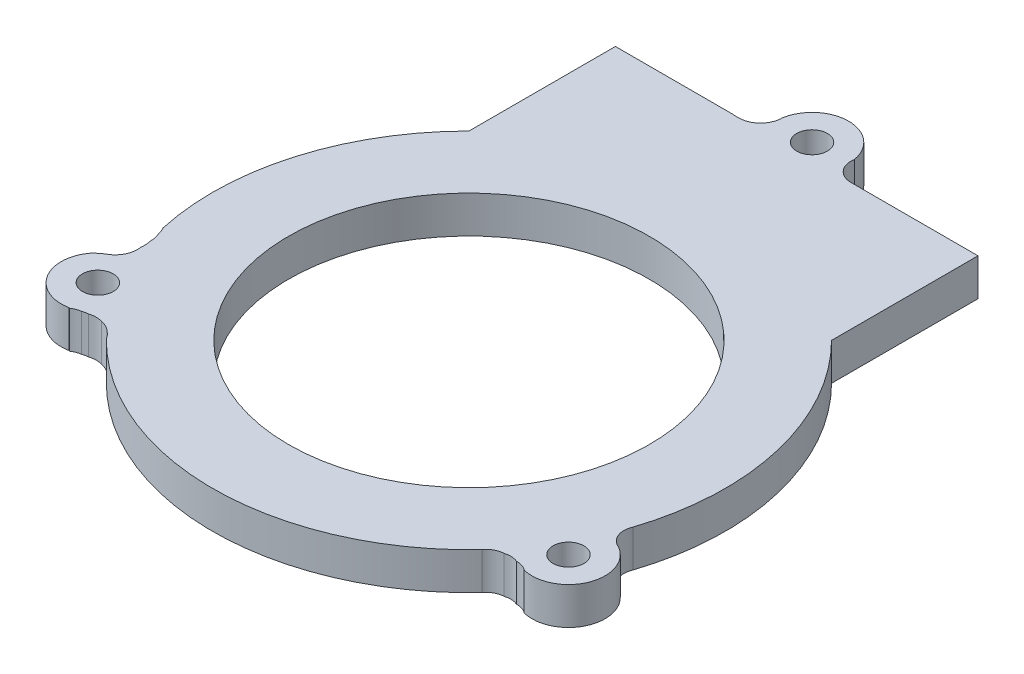
SolidWorks part; units mm, degrees
ref_plane "Front Plane" through (0, 0, 0) normal (0, 0, 1) x (1, 0, 0)
ref_plane "Top Plane" through (0, 0, 0) normal (0, 1, 0) x (1, 0, 0)
ref_plane "Right Plane" through (0, 0, 0) normal (1, 0, 0) x (0, 0, -1)
sketch "Sketch13" plane through (0, 0, 0) normal (0, 1, 0) x (1, 0, 0)
  circle A0 centre (0, 0) radius 35
extrude "Boss-Extrude3" add sketch "Sketch13" along normal blind 5.08
sketch "Sketch14" plane through (0, 5.08, 0) normal (0, 1, 0) x (1, 0, 0)
  line L0 (-24.7478, 24.7497) -> (24.7477, 24.7498)
  line L1 (-24.7478, 24.7497) -> (-24.7479, 44.7452)
  line L2 (24.7477, 24.7498) -> (24.7476, 44.7454)
  line L3 (-24.7479, 44.7452) -> (24.7476, 44.7454)
  line L4 (0, 0) -> (60.4611, -34.8658) construction
  line L5 (0, 0) -> (-56.6044, -32.6614) construction
  line L7 (-3.939, 44.1714) -> (-8.8985, 44.1714)
  line L8 (-3.939, 44.1714) -> (-3.939, 47.547)
  line L9 (-3.939, 47.547) -> (-8.8985, 47.547)
  line L10 (-8.8985, 44.1714) -> (-8.8985, 47.547)
  arc A0 (0, 35) -> (-24.7478, 24.7497) centre (0, 0) ccw construction
  circle A1 centre (0, 0) radius 35 construction
  arc A2 (0, 35) -> (-30.3109, -17.4999) centre (0, 0) ccw construction
  arc A3 (0, 35) -> (30.3118, -17.4984) centre (0, 0) ccw
  arc A4 (0, 35) -> (24.7477, 24.7498) centre (0, 0) ccw construction
  circle A5 centre (32.1365, -18.5413) radius 2.1017
  circle A6 centre (32.1365, -18.5413) radius 4.9951
  circle A7 centre (-32.1465, -18.5162) radius 2.0981
  circle A8 centre (-32.1465, -18.5162) radius 4.9995
extrude "Boss-Extrude4" add sketch "Sketch14" against normal up to surface (5.08 mm away) contours L0 L1 L3 L2 up to face at (0, 0, 35)
sketch "Sketch15" plane through (0, 5.08, 0) normal (0, 1, 0) x (1, 0, 0)
  line L0 (0, 0) -> (0, 62.3966) construction
  line L1 (-0.0001, 44.7453) -> (0, 46.8414) construction
  line L2 (-24.7479, 44.7452) -> (24.7476, 44.7454) construction
  circle A0 centre (0, 46.8414) radius 2.0961
  circle A1 centre (0, 46.8414) radius 4.996
extrude "Boss-Extrude11" add sketch "Sketch15" against normal blind 5.08 contours A1 | A0
extrude "Boss-Extrude12" add sketch "Sketch14<6>" against normal up to surface (5.08 mm away) contours A6 up to face at (0, 0, -29.3038)
sketch "Sketch14<6>" plane through (0, 5.08, 0) normal (0, 1, 0) x (1, 0, 0) same geometry as "Sketch14"
extrude "Boss-Extrude14" add sketch "Sketch14<8>" against normal through all contours L0 A5 region at (32.1365, 5.08, 18.5413)
sketch "Sketch14<8>" plane through (0, 5.08, 0) normal (0, 1, 0) x (1, 0, 0) same geometry as "Sketch14"
hole_wizard "Ø4.2 (4.2) Diameter Hole1" positions "Sketch22" profile "Sketch23" hole size "Ø4.2" standard "ANSI Metric" end condition through all
sketch "Sketch22" plane through (0, 5.08, 0) normal (0, 1, 0) x (1, 0, 0)
  point P0 (32.1248, -18.5356)
sketch "Sketch23" plane through (32.1248, 5.08, 18.5356) normal (1, 0, 0) x (0, 0, 1)
  line L0 (0, 0) -> (0, 5.08)
  line L1 (0, 5.08) -> (2.1, 5.08)
  line L2 (2.1, 5.08) -> (2.1, 0)
  line L5 (2.1, 0) -> (0, 0)
  line L11 (0, -6.35) -> (0, 107.95) construction
  dimension "Thru Hole Dia." = 4.2
  dimension "Thru Hole Depth" = 5.08
extrude "Boss-Extrude15" add sketch "Sketch14<11>" against normal up to surface (5.08 mm away) contours A8 up to face at (32.1248, 0, 20.6356)
sketch "Sketch14<11>" plane through (0, 5.08, 0) normal (0, 1, 0) x (1, 0, 0) same geometry as "Sketch14"
hole_wizard "Ø4.2 (4.2) Diameter Hole2" positions "Sketch26" profile "Sketch27" hole size "Ø4.2" standard "ANSI Metric" end condition through all
sketch "Sketch26" plane through (0, 5.08, 0) normal (0, 1, 0) x (1, 0, 0)
  point P0 (-32.148, -18.5088)
  point P2 (-32.148, -18.5088)
sketch "Sketch27" plane through (-32.148, 5.08, 18.5088) normal (1, 0, 0) x (0, 0, 1)
  line L0 (0, 0) -> (0, 5.08)
  line L1 (0, 5.08) -> (2.1, 5.08)
  line L2 (2.1, 5.08) -> (2.1, 0)
  line L5 (2.1, 0) -> (0, 0)
  line L11 (0, -6.35) -> (0, 107.95) construction
  dimension "Thru Hole Dia." = 4.2
  dimension "Thru Hole Depth" = 5.08
sketch "Sketch35" plane through (0, 5.08, 0) normal (0, 1, 0) x (1, 0, 0)
  line L1 (2.8641, 47.653) -> (7.6285, 47.653)
  line L2 (2.8641, 47.653) -> (2.8641, 41.8007)
  line L3 (2.8641, 41.8007) -> (7.6285, 41.8007)
  line L4 (7.6285, 47.653) -> (7.6285, 41.8007)
extrude "Boss-Extrude17" add sketch "Sketch35" against normal up to surface (5.08 mm away) up to face at (-32.148, 0, 20.6088)
hole_wizard "Ø5.0 (5) Diameter Hole2" positions "Sketch36" profile "Sketch37" hole size "Ø5.0" standard "ANSI Metric" end condition through all
sketch "Sketch36" plane through (0, 5.08, 0) normal (0, 1, 0) x (1, 0, 0)
  point P0 (7.3825, 47.2405)
sketch "Sketch37" plane through (7.3825, 5.08, -47.2405) normal (1, 0, 0) x (0, 0, 1)
  line L0 (0, 0) -> (0, 5.08)
  line L1 (0, 5.08) -> (2.5, 5.08)
  line L2 (2.5, 5.08) -> (2.5, 0)
  line L5 (2.5, 0) -> (0, 0)
  line L11 (0, -6.35) -> (0, 107.95) construction
  dimension "Thru Hole Dia." = 5
  dimension "Thru Hole Depth" = 5.08
sketch "Sketch40" plane through (0, 5.08, 0) normal (0, 1, 0) x (1, 0, 0)
  line L1 (-4.0169, 44.4311) -> (-8.6129, 44.4311)
  line L2 (-4.0169, 44.4311) -> (-4.0169, 47.7807)
  line L3 (-4.0169, 47.7807) -> (-8.6129, 47.7807)
  line L4 (-8.6129, 44.4311) -> (-8.6129, 47.7807)
extrude "Boss-Extrude18" add sketch "Sketch40" against normal up to surface (5.08 mm away) up to face at (1.1009, 0, -19.7795)
hole_wizard "Ø6.0 (6) Diameter Hole1" positions "Sketch41" profile "Sketch42" hole size "Ø6.0" standard "ANSI Metric" end condition through all
sketch "Sketch41" plane through (0, 5.08, 0) normal (0, 1, 0) x (1, 0, 0)
  point P0 (-7.9034, 47.7108)
  point P2 (-8.2468, 47.7108)
sketch "Sketch42" plane through (-7.9034, 5.08, -47.7108) normal (1, 0, 0) x (0, 0, 1)
  line L0 (0, 0) -> (0, 5.08)
  line L1 (0, 5.08) -> (3, 5.08)
  line L2 (3, 5.08) -> (3, 0)
  line L5 (3, 0) -> (0, 0)
  line L11 (0, -6.35) -> (0, 107.95) construction
  dimension "Thru Hole Dia." = 6
  dimension "Thru Hole Depth" = 5.08
sketch "Sketch49" plane through (0, 5.08, 0) normal (0, 1, 0) x (1, 0, 0)
  line L0 (34.8609, -15.3439) -> (32.14, -8.6999)
  line L1 (34.8609, -15.3439) -> (33.4371, -16.7043)
  line L2 (32.14, -8.6999) -> (30.7163, -10.0603)
  line L3 (33.4371, -16.7043) -> (30.7163, -10.0603)
extrude "Boss-Extrude21" add sketch "Sketch49" against normal up to surface (5.08 mm away) up to face at (-0.1098, 0, -23.418)
sketch "Sketch50" plane through (0, 5.08, 0) normal (0, 1, 0) x (1, 0, 0)
  line L0 (35.9043, -11.4293) -> (30.8001, -13.8003)
  line L1 (35.9043, -11.4293) -> (36.4392, -11.7775)
  line L2 (30.8001, -13.8003) -> (31.3349, -14.1485)
  line L3 (36.4392, -11.7775) -> (31.3349, -14.1485)
extrude "Boss-Extrude22" add sketch "Sketch50" against normal up to surface (5.08 mm away) up to face at (2.0878, 0, -21.0396)
hole_wizard "Ø5.0 (5) Diameter Hole3" positions "Sketch53" profile "Sketch54" hole size "Ø5.0" standard "ANSI Metric" end condition through all
sketch "Sketch53" plane through (0, 5.08, 0) normal (0, 1, 0) x (1, 0, 0)
  point P0 (35.5521, -11.8954)
sketch "Sketch54" plane through (35.5521, 5.08, 11.8954) normal (1, 0, 0) x (0, 0, 1)
  line L0 (0, 0) -> (0, 5.08)
  line L1 (0, 5.08) -> (2.5, 5.08)
  line L2 (2.5, 5.08) -> (2.5, 0)
  line L5 (2.5, 0) -> (0, 0)
  line L11 (0, -6.35) -> (0, 107.95) construction
  dimension "Thru Hole Dia." = 5
  dimension "Thru Hole Depth" = 5.08
sketch "Sketch56" plane through (0, 5.08, 0) normal (0, 1, 0) x (1, 0, 0)
  line L0 (31.7446, -23.1438) -> (24.6321, -23.4721)
  line L1 (31.7446, -23.1438) -> (29.5561, -20.1529)
  line L2 (24.6321, -23.4721) -> (22.4437, -20.4812)
  line L3 (29.5561, -20.1529) -> (22.4437, -20.4812)
extrude "Boss-Extrude23" add sketch "Sketch56" against normal up to surface (5.08 mm away) up to face at (2.0435, 0, -21.0249)
sketch "Sketch59" plane through (0, 5.08, 0) normal (0, 1, 0) x (1, 0, 0)
  line L0 (27.6314, -22.3273) -> (29.7257, -24.2832)
  line L1 (27.6314, -22.3273) -> (26.7832, -22.7168)
  line L2 (29.7257, -24.2832) -> (28.8776, -24.6727)
  line L3 (26.7832, -22.7168) -> (28.8776, -24.6727)
extrude "Boss-Extrude24" add sketch "Sketch59" against normal up to surface (5.08 mm away) up to face at (3.6446, 0, -18.3394)
sketch "Sketch62" plane through (0, 5.08, 0) normal (0, 1, 0) x (1, 0, 0)
  line L0 (29.1515, -23.0329) -> (27.8189, -25.204)
  line L1 (29.1515, -23.0329) -> (28.2027, -21.1977)
  line L2 (27.8189, -25.204) -> (26.87, -23.3688)
  line L3 (28.2027, -21.1977) -> (26.87, -23.3688)
  line L4 (26.0205, -23.408) -> (27.4526, -23.3419) construction
extrude "Boss-Extrude25" add sketch "Sketch62" against normal up to surface (5.08 mm away) up to face at (8.6514, 0, -9.8923)
sketch "Sketch65" plane through (0, 5.08, 0) normal (0, 1, 0) x (1, 0, 0)
  line L0 (27.8997, -23.9063) -> (29.8692, -24.8473)
  line L1 (27.8997, -23.9063) -> (26.9587, -24.9348)
  line L2 (29.8692, -24.8473) -> (28.9282, -25.8758)
  line L3 (26.9587, -24.9348) -> (28.9282, -25.8758)
extrude "Boss-Extrude26" add sketch "Sketch65" against normal up to surface (5.08 mm away) up to face at (11.2129, 0, -5.4308)
sketch "Sketch68" plane through (0, 5.08, 0) normal (0, 1, 0) x (1, 0, 0)
  line L0 (30.9127, -22.8129) -> (25.2547, -23.1255)
  line L1 (30.9127, -22.8129) -> (30.9127, -23.5631)
  line L2 (25.2547, -23.1255) -> (25.2547, -23.8757)
  line L3 (30.9127, -23.5631) -> (25.2547, -23.8757)
extrude "Boss-Extrude27" add sketch "Sketch68" against normal up to surface (5.08 mm away) up to face at (12.6064, 0, -2.9763)
hole_wizard "Ø5.0 (5) Diameter Hole6" positions "Sketch69" profile "Sketch70" hole size "Ø5.0" standard "ANSI Metric" end condition through all
sketch "Sketch69" plane through (0, 5.08, 0) normal (0, 1, 0) x (1, 0, 0)
  line L0 (28.9282, -25.8758) -> (29.8692, -24.8473) construction
  line L1 (26.9587, -24.9348) -> (28.9282, -25.8758) construction
  point P0 (29.3987, -25.3616)
  point P4 (27.6814, -25.2801)
  point P8 (28.3685, -25.1602)
sketch "Sketch70" plane through (29.3987, 5.08, 25.3616) normal (1, 0, 0) x (0, 0, 1)
  line L0 (0, 0) -> (0, 5.08)
  line L1 (0, 5.08) -> (2.5, 5.08)
  line L2 (2.5, 5.08) -> (2.5, 0)
  line L5 (2.5, 0) -> (0, 0)
  line L11 (0, -6.35) -> (0, 107.95) construction
  dimension "Thru Hole Dia." = 5
  dimension "Thru Hole Depth" = 5.08
sketch "Sketch71" plane through (0, 5.08, 0) normal (0, 1, 0) x (1, 0, 0)
  line L0 (-30.5842, -23.0334) -> (-28.8636, -25.0717)
  line L1 (-30.5842, -23.0334) -> (-27.4076, -20.651)
  line L2 (-28.8636, -25.0717) -> (-25.687, -22.6893)
  line L3 (-27.4076, -20.651) -> (-25.687, -22.6893)
extrude "Boss-Extrude28" add sketch "Sketch71" against normal up to surface (5.08 mm away) up to face at (7.4065, 0, -11.8126)
sketch "Sketch74" plane through (0, 5.08, 0) normal (0, 1, 0) x (1, 0, 0)
  line L0 (-30.6707, -23.0812) -> (-27.2241, -20.8929)
  line L1 (-30.6707, -23.0812) -> (-29.0322, -26.0708)
  line L2 (-27.2241, -20.8929) -> (-25.5856, -23.8825)
  line L3 (-29.0322, -26.0708) -> (-25.5856, -23.8825)
  arc A0 (-26.2706, -23.1269) -> (25.6103, -23.8561) centre (0, 0) ccw construction
extrude "Boss-Extrude29" add sketch "Sketch74" against normal up to surface (5.08 mm away) up to face at (4.01, 0, -8.4625)
sketch "Sketch81" plane through (0, 5.08, 0) normal (0, 1, 0) x (1, 0, 0)
  line L0 (-32.1571, -22.5423) -> (-23.5245, -23.9395)
  line L1 (-32.1571, -22.5423) -> (-32.2041, -23.2575)
  line L2 (-23.5245, -23.9395) -> (-23.5714, -24.6547)
  line L3 (-32.2041, -23.2575) -> (-23.5714, -24.6547)
extrude "Boss-Extrude31" add sketch "Sketch81" against normal up to surface (5.08 mm away) contours L3 L2 L0 L1 up to face at (4.0386, 0, -8.3991)
sketch "Sketch88" plane through (0, 5.08, 0) normal (0, 1, 0) x (1, 0, 0)
  line L0 (-31.2768, -22.9708) -> (-28.8815, -27.1015)
  line L1 (-31.2768, -22.9708) -> (-27.0233, -20.2385)
  line L2 (-28.8815, -27.1015) -> (-24.628, -24.3693)
  line L3 (-27.0233, -20.2385) -> (-24.628, -24.3693)
extrude "Boss-Extrude32" add sketch "Sketch88" against normal up to surface (5.08 mm away) up to face at (1.2398, 0, -5.5899)
hole_wizard "Ø6.0 (6) Diameter Hole6" positions "3DSketch1" profile "Sketch89" hole size "Ø6.0" standard "ANSI Metric" end condition through all
sketch3d "3DSketch1"
  point P0 (-29.4228, 5.08, 25.9655)
  point P2 (-27.5354, 5.08, 26.0591)
  point P4 (-28.9081, 5.08, 25.8407)
  point P6 (-28.1749, 5.08, 25.7003)
  point P8 (-27.863, 5.08, 25.7783)
sketch "Sketch89" plane through (-29.4228, 5.08, 25.9655) normal (1, 0, 0) x (0, 0, 1)
  line L0 (0, 0) -> (0, 5.08)
  line L1 (0, 5.08) -> (3, 5.08)
  line L2 (3, 5.08) -> (3, 0)
  line L5 (3, 0) -> (0, 0)
  line L11 (0, -6.35) -> (0, 107.95) construction
  dimension "Thru Hole Dia." = 6
  dimension "Thru Hole Depth" = 5.08
sketch "Sketch90" plane through (0, 5.08, 0) normal (0, 1, 0) x (1, 0, 0)
  line L0 (-35.8257, -16.1298) -> (-36.7606, -9.0025)
  line L1 (-35.8257, -16.1298) -> (-30.6487, -13.2047)
  line L2 (-36.7606, -9.0025) -> (-31.5836, -6.0773)
  line L3 (-30.6487, -13.2047) -> (-31.5836, -6.0773)
extrude "Boss-Extrude33" add sketch "Sketch90" against normal up to surface (5.08 mm away) up to face at (-2.0626, 0, -2.3998)
sketch "Sketch92" plane through (0, 5.08, 0) normal (0, 1, 0) x (1, 0, 0)
  line L0 (-36.1966, -9.3612) -> (-36.9791, -9.8106)
  line L1 (-36.1966, -9.3612) -> (-36.4965, -11.4282)
  line L2 (-36.9791, -9.8106) -> (-37.279, -11.8776)
  line L3 (-36.4965, -11.4282) -> (-37.279, -11.8776)
extrude "Boss-Extrude34" add sketch "Sketch92" against normal up to surface (5.08 mm away) up to face at (-4.4305, 0, -1.5384)
sketch "Sketch95" plane through (0, 5.08, 0) normal (0, 1, 0) x (1, 0, 0)
  line L0 (-36.1775, -9.8864) -> (-38.6117, -11.1465)
  line L1 (-36.1775, -9.8864) -> (-34.9904, -12.627)
  line L2 (-38.6117, -11.1465) -> (-37.4246, -13.8871)
  line L3 (-34.9904, -12.627) -> (-37.4246, -13.8871)
extrude "Boss-Extrude35" add sketch "Sketch95" against normal up to surface (5.08 mm away) up to face at (-9.332, 0, 0.3306)
hole_wizard "Ø6.0 (6) Diameter Hole7" positions "Sketch96" profile "Sketch97" hole size "Ø6.0" standard "ANSI Metric" end condition through all
sketch "Sketch96" plane through (0, 5.08, 0) normal (0, 1, 0) x (1, 0, 0)
  line L0 (-36.7606, -9.0025) -> (-36.6773, -9.6373) construction
  point P0 (-37.2637, -12.5458)
  point P2 (-36.3719, -11.9088)
  point P4 (-36.7458, -9.1153)
  point P8 (-36.4834, -9.9022)
  point P10 (-36.3719, -10.9055)
sketch "Sketch97" plane through (-37.2637, 5.08, 12.5458) normal (1, 0, 0) x (0, 0, 1)
  line L0 (0, 0) -> (0, 5.08)
  line L1 (0, 5.08) -> (3, 5.08)
  line L2 (3, 5.08) -> (3, 0)
  line L5 (3, 0) -> (0, 0)
  line L11 (0, -6.35) -> (0, 107.95) construction
  dimension "Thru Hole Dia." = 6
  dimension "Thru Hole Depth" = 5.08
hole_wizard "Ø10.0 (10) Diameter Hole1" positions "Sketch98" profile "Sketch99" hole size "Ø10.0" standard "ANSI Metric" end condition through all
sketch "Sketch98" plane through (0, 5.08, 0) normal (0, 1, 0) x (1, 0, 0)
  point P0 (0, 0)
sketch "Sketch99" plane through (0, 5.08, 0) normal (1, 0, 0) x (0, 0, 1)
  line L0 (0, 0) -> (0, 5.08)
  line L1 (0, 5.08) -> (5, 5.08)
  line L2 (5, 5.08) -> (5, 0)
  line L5 (5, 0) -> (0, 0)
  line L11 (0, -6.35) -> (0, 107.95) construction
  dimension "Thru Hole Dia." = 10
  dimension "Thru Hole Depth" = 5.08
sketch "Sketch100" plane through (0, 5.08, 0) normal (0, 1, 0) x (1, 0, 0)
  circle A0 centre (0, 0) radius 24.6297
extrude "Cut-Extrude1" cut sketch "Sketch100" against normal through all
